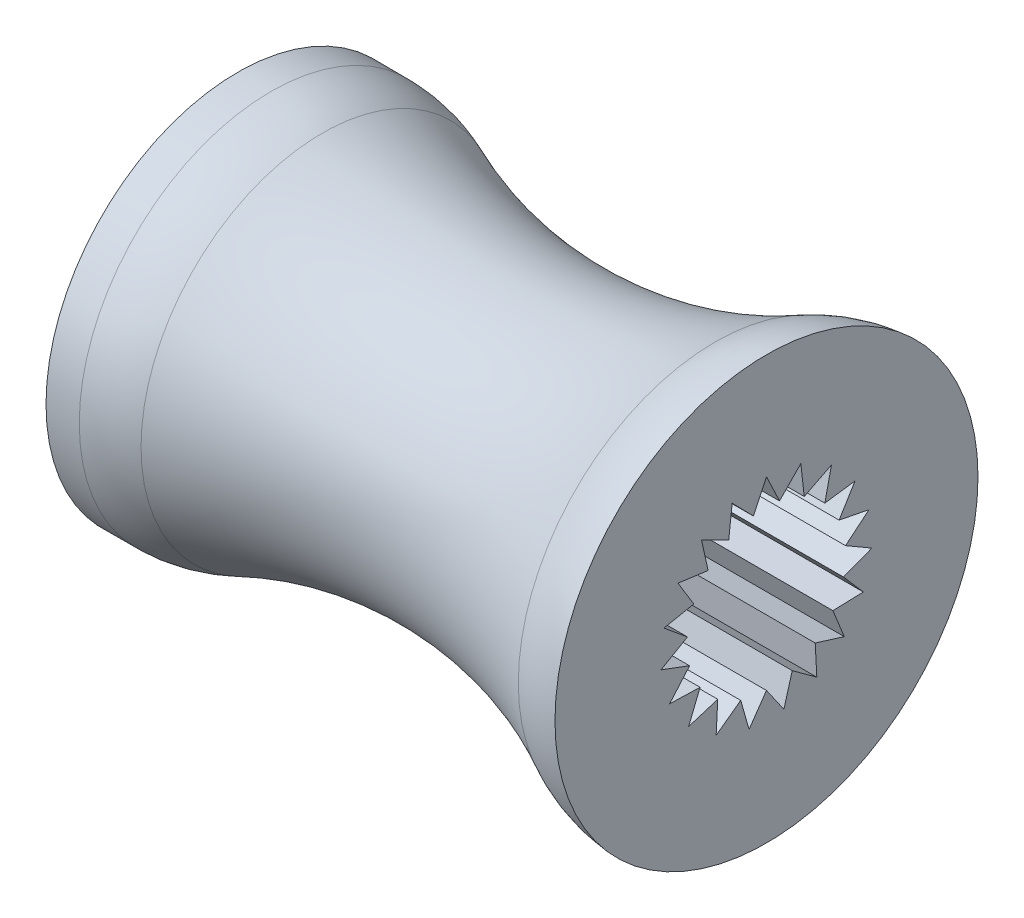
SolidWorks part; units mm, degrees
ref_plane "Front Plane" through (0, 0, 0) normal (0, 0, 1) x (1, 0, 0)
ref_plane "Top Plane" through (0, 0, 0) normal (0, 1, 0) x (1, 0, 0)
ref_plane "Right Plane" through (0, 0, 0) normal (1, 0, 0) x (0, 0, -1)
other "Configuration Table"
sketch "Sketch1" plane through (0, 0, 0) normal (0, 0, 1) x (1, 0, 0)
  line L0 (-20, 4.7625) -> (-20, 14.5)
  line L1 (-20, 0) -> (20, 0) construction
  line L2 (-16.825, 4.7625) -> (-16.825, 3.9688)
  line L3 (-16.825, 3.9688) -> (16.825, 3.9688)
  line L4 (20, 4.7625) -> (20, 16)
  line L5 (-20, 4.7625) -> (-16.825, 4.7625)
  line L6 (16.825, 3.9688) -> (16.825, 4.7625)
  line L7 (16.825, 4.7625) -> (20, 4.7625)
  line L8 (20, 16) -> (18.0862, 16)
  line L10 (-20, 14.5) -> (-15.3286, 14.5)
  arc A0 (18.0862, 16) -> (-15.3286, 14.5) centre (0, 45.9648) cw
  point P13 (1.5696, 11)
  dimension "D1" = 35
  dimension "D2" = 9.525
  dimension "D3" = 32
  dimension "D4" = 40
  dimension "D5" = 7.9375
  dimension "D6" = 3.175
  dimension "D7" = 22
  dimension "D8" = 29
revolve "Revolve1" add sketch "Sketch1" angle 360 about L1
sketch "Sketch2" plane through (20, 0, 0) normal (1, 0, 0) x (0, 0, -1)
  line L0 (-0.9876, 5.9182) -> (0, 8)
  line L1 (0, 4.7625) -> (0, 14.5) construction
  line L2 (0, 8) -> (0.9876, 5.9182)
  line L3 (0.9876, 5.9182) -> (2.5976, 7.5665)
  line L4 (2.5976, 7.5665) -> (2.8557, 5.2768)
  line L5 (2.8557, 5.2768) -> (4.9137, 6.3131)
  line L6 (4.9137, 6.3131) -> (4.4143, 4.0637)
  line L7 (4.4143, 4.0637) -> (6.6973, 4.3756)
  line L8 (6.6973, 4.3756) -> (5.4946, 2.4102)
  line L9 (5.4946, 2.4102) -> (7.7552, 1.9639)
  line L10 (7.7552, 1.9639) -> (5.9795, 0.4955)
  line L11 (5.9795, 0.4955) -> (7.9727, -0.6606)
  line L12 (7.9727, -0.6606) -> (5.8164, -1.4729)
  line L13 (5.8164, -1.4729) -> (7.3262, -3.2136)
  line L14 (7.3262, -3.2136) -> (5.023, -3.2817)
  line L15 (5.023, -3.2817) -> (5.8858, -5.4183)
  line L16 (5.8858, -5.4183) -> (3.6853, -4.7348)
  line L17 (3.6853, -4.7348) -> (3.8076, -7.0358)
  line L18 (3.8076, -7.0358) -> (1.9482, -5.6749)
  line L19 (1.9482, -5.6749) -> (1.3168, -7.8909)
  line L20 (1.3168, -7.8909) -> (0, -6)
  line L21 (0, -6) -> (-1.3168, -7.8909)
  line L22 (-1.3168, -7.8909) -> (-1.9482, -5.6749)
  line L23 (-1.9482, -5.6749) -> (-3.8076, -7.0358)
  line L24 (-3.8076, -7.0358) -> (-3.6853, -4.7348)
  line L25 (-3.6853, -4.7348) -> (-5.8858, -5.4183)
  line L26 (-5.8858, -5.4183) -> (-5.023, -3.2817)
  line L27 (-5.023, -3.2817) -> (-7.3262, -3.2136)
  line L28 (-7.3262, -3.2136) -> (-5.8164, -1.4729)
  line L29 (-5.8164, -1.4729) -> (-7.9727, -0.6606)
  line L30 (-7.9727, -0.6606) -> (-5.9795, 0.4955)
  line L31 (-5.9795, 0.4955) -> (-7.7552, 1.9639)
  line L32 (-7.7552, 1.9639) -> (-5.4946, 2.4102)
  line L33 (-5.4946, 2.4102) -> (-6.6973, 4.3756)
  line L34 (-6.6973, 4.3756) -> (-4.4143, 4.0637)
  line L35 (-4.4143, 4.0637) -> (-4.9137, 6.3131)
  line L36 (-4.9137, 6.3131) -> (-2.8557, 5.2768)
  line L37 (-2.8557, 5.2768) -> (-2.5976, 7.5665)
  line L38 (-2.5976, 7.5665) -> (-0.9876, 5.9182)
  circle A0 centre (0, 0) radius 6 construction
  point P64 (0, 0)
  dimension "D3" = 12
  dimension "D1" = 8
  dimension "D4" = 19
extrude "Cut-Extrude1" cut sketch "Sketch2" against normal through all
fillet "Fillet1" radius 10 2 edges at (18.0862, 0, 16) (-15.3286, 0, 14.5)
